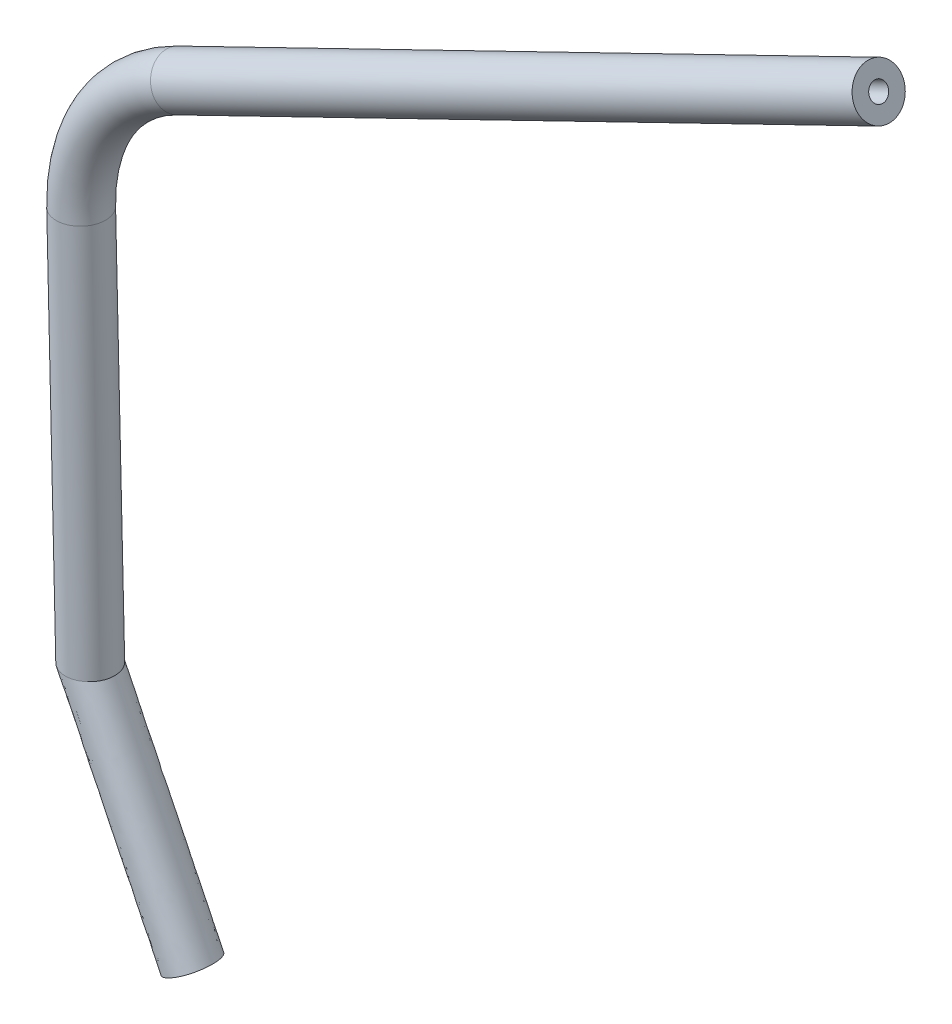
SolidWorks part; units mm, degrees
material "Cast Carbon Steel"
ref_plane "Front Plane" through (0, 0, 0) normal (0, 0, 1) x (1, 0, 0)
ref_plane "Top Plane" through (0, 0, 0) normal (0, 1, 0) x (1, 0, 0)
ref_plane "Right Plane" through (0, 0, 0) normal (1, 0, 0) x (0, 0, -1)
sketch "Sketch4" plane through (0, 0, 0) normal (0, 0, 1) x (1, 0, 0)
  arc A0 (-38.8747, 79.9498) -> (-88.8758, -2.0729) centre (0, 0) ccw
  dimension "D1" = 88.9
sketch "Sketch5" plane through (0, 0, 0) normal (0, 1, 0) x (1, 0, 0)
  circle A0 centre (-88.8758, 0) radius 12.7
  circle A1 centre (-88.8758, 0) radius 4.7625
  dimension "D1" = 25.4
  dimension "D2" = 7.9375
sweep "Sweep1" add profiles "Sketch5" path "Sketch4"
ref_plane "Plane4" through (0, 0, 0) normal (0.8993, 0.4373, 0) x (0, 0, -1)
sketch "Sketch6" plane through (0, 0, 0) normal (0.8993, 0.4373, 0) x (0, 0, -1)
  circle A0 centre (0, 88.8758) radius 12.7
  circle A1 centre (0, 88.8758) radius 4.7625
  dimension "D1" = 7.9375
extrude "Boss-Extrude3" add sketch "Sketch6" along normal blind 406.4
ref_plane "Plane5" through (0, 0, 0) normal (0.0233, -0.9997, 0) x (-0.9997, -0.0233, 0)
sketch "Sketch7" plane through (0, 0, 0) normal (0.0233, -0.9997, 0) x (-0.9997, -0.0233, 0)
  circle A0 centre (88.8758, 0) radius 12.7
  circle A1 centre (88.8758, 0) radius 4.7625
  dimension "D1" = 7.9375
  dimension "D2" = 25.4
extrude "Boss-Extrude4" add sketch "Sketch7" along normal blind 203.2
ref_plane "Plane7" through (0, 0, -12.7) normal (0, 0, -1) x (-1, 0, 0)
sketch "Sketch9" plane through (0, 0, -12.7) normal (0, 0, -1) x (-1, 0, 0)
  line L0 (33.3106, 68.5067) -> (44.4176, 91.3495) construction
  line L1 (76.1551, -1.7762) -> (101.5482, -2.3685) construction
  circle A0 centre (76.2699, 46.4942) radius 12.7
  dimension "D1" = 25.4
  dimension "D2" = 48.26
  dimension "D3" = 48.26
extrude "Cut-Extrude2" cut sketch "Sketch9" against normal blind 6.35
ref_plane "Plane8" through (4.7381, -203.1448, 0) normal (0.0233, -0.9997, 0) x (-0.9997, -0.0233, 0)
sketch "Sketch10" plane through (4.7381, -203.1448, 0) normal (0.0233, -0.9997, 0) x (-0.9997, -0.0233, 0)
  circle A0 centre (88.8758, 0) radius 12.7
  circle A1 centre (88.8758, 0) radius 4.7625
  circle A2 centre (88.8758, 0) radius 12.7 construction
  dimension "D1" = 7.9375
sketch "Sketch11" plane through (0, 0, 0) normal (0, 0, 1) x (1, 0, 0)
  line L0 (-84.1136, -205.2171) -> (-28.5784, -319.4311)
  line L1 (24.0507, -49.4628) -> (-24.0507, 49.4628) construction
  dimension "D1" = 127
sweep "Sweep2" add profiles "Sketch10" path "Sketch11"
sketch "Sketch12" plane through (0, 0, 0) normal (0, 0, 1) x (1, 0, 0)
  line L0 (-41.2749, -319.7272) -> (-20.5045, -309.6279)
  line L1 (-15.8818, -319.135) -> (-71.417, -204.921) construction
  line L2 (-20.5045, -309.6279) -> (-15.8818, -319.135)
  line L3 (-15.8818, -319.135) -> (-41.2749, -319.7272)
extrude "Cut-Extrude3" cut sketch "Sketch12" against normal through all both and the other way through all
